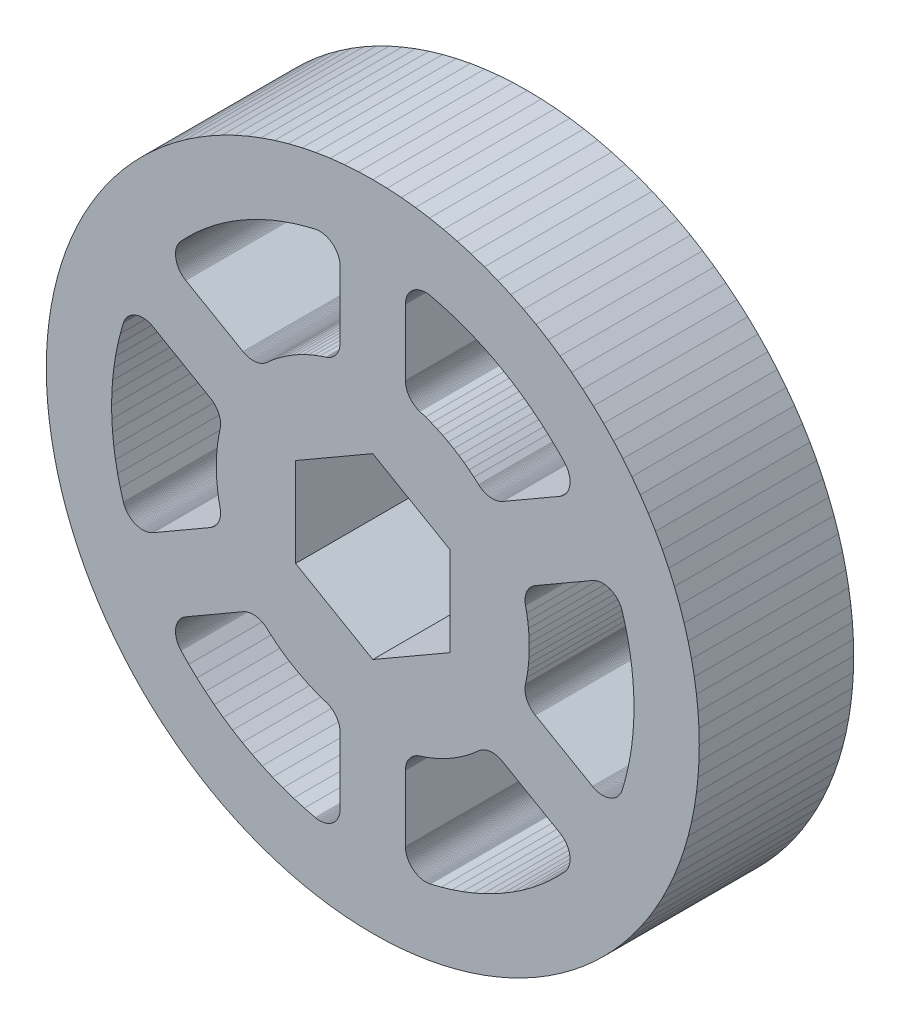
SolidWorks part; units mm, degrees
ref_plane "Front" through (0, 0, 0) normal (0, 0, 1) x (1, 0, 0)
ref_plane "Top" through (0, 0, 0) normal (0, 1, 0) x (1, 0, 0)
ref_plane "Right" through (0, 0, 0) normal (1, 0, 0) x (0, 0, -1)
ref_plane "Plane1" through (0, 0, 12.7) normal (0, 0, 1) x (1, 0, 0)
sketch "Sketch1" plane through (0, 0, 12.7) normal (0, 0, 1) x (1, 0, 0)
  line L0 (19.796, 18.1397) -> (18.9859, 18.9859)
  line L1 (18.9859, 18.9859) -> (18.1397, 19.796)
  line L2 (18.1397, 19.796) -> (17.2589, 20.5684)
  line L3 (17.2589, 20.5684) -> (16.3453, 21.3016)
  line L4 (16.3453, 21.3016) -> (15.4006, 21.9943)
  line L5 (15.4006, 21.9943) -> (14.4265, 22.6451)
  line L6 (14.4265, 22.6451) -> (13.425, 23.2529)
  line L7 (13.425, 23.2529) -> (12.398, 23.8163)
  line L8 (12.398, 23.8163) -> (11.3473, 24.3344)
  line L9 (11.3473, 24.3344) -> (10.2751, 24.8062)
  line L10 (10.2751, 24.8062) -> (9.1833, 25.2308)
  line L11 (9.1833, 25.2308) -> (8.074, 25.6074)
  line L12 (8.074, 25.6074) -> (6.9493, 25.9352)
  line L13 (6.9493, 25.9352) -> (5.8114, 26.2136)
  line L14 (5.8114, 26.2136) -> (4.6625, 26.4422)
  line L15 (4.6625, 26.4422) -> (3.5046, 26.6204)
  line L16 (3.5046, 26.6204) -> (2.3401, 26.7479)
  line L17 (2.3401, 26.7479) -> (1.1712, 26.8245)
  line L18 (1.1712, 26.8245) -> (0, 26.8501)
  line L19 (0, 26.8501) -> (-1.1712, 26.8245)
  line L20 (-1.1712, 26.8245) -> (-2.3401, 26.7479)
  line L21 (-2.3401, 26.7479) -> (-3.5046, 26.6204)
  line L22 (-3.5046, 26.6204) -> (-4.6625, 26.4422)
  line L23 (-4.6625, 26.4422) -> (-5.8114, 26.2136)
  line L24 (-5.8114, 26.2136) -> (-6.9493, 25.9352)
  line L25 (-6.9493, 25.9352) -> (-8.074, 25.6074)
  line L26 (-8.074, 25.6074) -> (-9.1833, 25.2308)
  line L27 (-9.1833, 25.2308) -> (-10.2751, 24.8062)
  line L28 (-10.2751, 24.8062) -> (-11.3473, 24.3344)
  line L29 (-11.3473, 24.3344) -> (-12.398, 23.8163)
  line L30 (-12.398, 23.8163) -> (-13.425, 23.2529)
  line L31 (-13.425, 23.2529) -> (-14.4265, 22.6451)
  line L32 (-14.4265, 22.6451) -> (-15.4006, 21.9943)
  line L33 (-15.4006, 21.9943) -> (-16.3453, 21.3016)
  line L34 (-16.3453, 21.3016) -> (-17.2589, 20.5684)
  line L35 (-17.2589, 20.5684) -> (-18.1397, 19.796)
  line L36 (-18.1397, 19.796) -> (-18.9859, 18.9859)
  line L37 (-18.9859, 18.9859) -> (-19.796, 18.1397)
  line L38 (-19.796, 18.1397) -> (-20.5684, 17.2589)
  line L39 (-20.5684, 17.2589) -> (-21.3016, 16.3453)
  line L40 (-21.3016, 16.3453) -> (-21.9943, 15.4006)
  line L41 (-21.9943, 15.4006) -> (-22.6451, 14.4265)
  line L42 (-22.6451, 14.4265) -> (-23.2529, 13.425)
  line L43 (-23.2529, 13.425) -> (-23.8163, 12.398)
  line L44 (-23.8163, 12.398) -> (-24.3344, 11.3473)
  line L45 (-24.3344, 11.3473) -> (-24.8062, 10.2751)
  line L46 (-24.8062, 10.2751) -> (-25.2308, 9.1833)
  line L47 (-25.2308, 9.1833) -> (-25.6074, 8.074)
  line L48 (-25.6074, 8.074) -> (-25.9352, 6.9493)
  line L49 (-25.9352, 6.9493) -> (-26.2136, 5.8114)
  line L50 (-26.2136, 5.8114) -> (-26.4422, 4.6625)
  line L51 (-26.4422, 4.6625) -> (-26.6204, 3.5046)
  line L52 (-26.6204, 3.5046) -> (-26.7479, 2.3401)
  line L53 (-26.7479, 2.3401) -> (-26.8245, 1.1712)
  line L54 (-26.8245, 1.1712) -> (-26.8501, 0)
  line L55 (-26.8501, 0) -> (-26.8245, -1.1712)
  line L56 (-26.8245, -1.1712) -> (-26.7479, -2.3401)
  line L57 (-26.7479, -2.3401) -> (-26.6204, -3.5046)
  line L58 (-26.6204, -3.5046) -> (-26.4422, -4.6625)
  line L59 (-26.4422, -4.6625) -> (-26.2136, -5.8114)
  line L60 (-26.2136, -5.8114) -> (-25.9352, -6.9493)
  line L61 (-25.9352, -6.9493) -> (-25.6074, -8.074)
  line L62 (-25.6074, -8.074) -> (-25.2308, -9.1833)
  line L63 (-25.2308, -9.1833) -> (-24.8062, -10.2751)
  line L64 (-24.8062, -10.2751) -> (-24.3344, -11.3473)
  line L65 (-24.3344, -11.3473) -> (-23.8163, -12.398)
  line L66 (-23.8163, -12.398) -> (-23.2529, -13.425)
  line L67 (-23.2529, -13.425) -> (-22.6451, -14.4265)
  line L68 (-22.6451, -14.4265) -> (-21.9943, -15.4006)
  line L69 (-21.9943, -15.4006) -> (-21.3016, -16.3453)
  line L70 (-21.3016, -16.3453) -> (-20.5684, -17.2589)
  line L71 (-20.5684, -17.2589) -> (-19.796, -18.1397)
  line L72 (-19.796, -18.1397) -> (-18.9859, -18.9859)
  line L73 (-18.9859, -18.9859) -> (-18.1397, -19.796)
  line L74 (-18.1397, -19.796) -> (-17.2589, -20.5684)
  line L75 (-17.2589, -20.5684) -> (-16.3453, -21.3016)
  line L76 (-16.3453, -21.3016) -> (-15.4006, -21.9943)
  line L77 (-15.4006, -21.9943) -> (-14.4265, -22.6451)
  line L78 (-14.4265, -22.6451) -> (-13.425, -23.2529)
  line L79 (-13.425, -23.2529) -> (-12.398, -23.8163)
  line L80 (-12.398, -23.8163) -> (-11.3473, -24.3344)
  line L81 (-11.3473, -24.3344) -> (-10.2751, -24.8062)
  line L82 (-10.2751, -24.8062) -> (-9.1833, -25.2308)
  line L83 (-9.1833, -25.2308) -> (-8.074, -25.6074)
  line L84 (-8.074, -25.6074) -> (-6.9493, -25.9352)
  line L85 (-6.9493, -25.9352) -> (-5.8114, -26.2136)
  line L86 (-5.8114, -26.2136) -> (-4.6625, -26.4422)
  line L87 (-4.6625, -26.4422) -> (-3.5046, -26.6204)
  line L88 (-3.5046, -26.6204) -> (-2.3401, -26.7479)
  line L89 (-2.3401, -26.7479) -> (-1.1712, -26.8245)
  line L90 (-1.1712, -26.8245) -> (0, -26.8501)
  line L91 (0, -26.8501) -> (1.1712, -26.8245)
  line L92 (1.1712, -26.8245) -> (2.3401, -26.7479)
  line L93 (2.3401, -26.7479) -> (3.5046, -26.6204)
  line L94 (3.5046, -26.6204) -> (4.6625, -26.4422)
  line L95 (4.6625, -26.4422) -> (5.8114, -26.2136)
  line L96 (5.8114, -26.2136) -> (6.9493, -25.9352)
  line L97 (6.9493, -25.9352) -> (8.074, -25.6074)
  line L98 (8.074, -25.6074) -> (9.1833, -25.2308)
  line L99 (9.1833, -25.2308) -> (10.2751, -24.8062)
  line L100 (10.2751, -24.8062) -> (11.3473, -24.3344)
  line L101 (11.3473, -24.3344) -> (12.398, -23.8163)
  line L102 (12.398, -23.8163) -> (13.425, -23.2529)
  line L103 (13.425, -23.2529) -> (14.4265, -22.6451)
  line L104 (14.4265, -22.6451) -> (15.4006, -21.9943)
  line L105 (15.4006, -21.9943) -> (16.3453, -21.3016)
  line L106 (16.3453, -21.3016) -> (17.2589, -20.5684)
  line L107 (17.2589, -20.5684) -> (18.1397, -19.796)
  line L108 (18.1397, -19.796) -> (18.9859, -18.9859)
  line L109 (18.9859, -18.9859) -> (19.796, -18.1397)
  line L110 (19.796, -18.1397) -> (20.5684, -17.2589)
  line L111 (20.5684, -17.2589) -> (21.3016, -16.3453)
  line L112 (21.3016, -16.3453) -> (21.9943, -15.4006)
  line L113 (21.9943, -15.4006) -> (22.6451, -14.4265)
  line L114 (22.6451, -14.4265) -> (23.2529, -13.425)
  line L115 (23.2529, -13.425) -> (23.8163, -12.398)
  line L116 (23.8163, -12.398) -> (24.3344, -11.3473)
  line L117 (24.3344, -11.3473) -> (24.8062, -10.2751)
  line L118 (24.8062, -10.2751) -> (25.2308, -9.1833)
  line L119 (25.2308, -9.1833) -> (25.6074, -8.074)
  line L120 (25.6074, -8.074) -> (25.9352, -6.9493)
  line L121 (25.9352, -6.9493) -> (26.2136, -5.8114)
  line L122 (26.2136, -5.8114) -> (26.4422, -4.6625)
  line L123 (26.4422, -4.6625) -> (26.6204, -3.5046)
  line L124 (26.6204, -3.5046) -> (26.7479, -2.3401)
  line L125 (26.7479, -2.3401) -> (26.8245, -1.1712)
  line L126 (26.8245, -1.1712) -> (26.8501, 0)
  line L127 (26.8501, 0) -> (26.8245, 1.1712)
  line L128 (26.8245, 1.1712) -> (26.7479, 2.3401)
  line L129 (26.7479, 2.3401) -> (26.6204, 3.5046)
  line L130 (26.6204, 3.5046) -> (26.4422, 4.6625)
  line L131 (26.4422, 4.6625) -> (26.2136, 5.8114)
  line L132 (26.2136, 5.8114) -> (25.9352, 6.9493)
  line L133 (25.9352, 6.9493) -> (25.6074, 8.074)
  line L134 (25.6074, 8.074) -> (25.2308, 9.1833)
  line L135 (25.2308, 9.1833) -> (24.8062, 10.2751)
  line L136 (24.8062, 10.2751) -> (24.3344, 11.3473)
  line L137 (24.3344, 11.3473) -> (23.8163, 12.398)
  line L138 (23.8163, 12.398) -> (23.2529, 13.425)
  line L139 (23.2529, 13.425) -> (22.6451, 14.4265)
  line L140 (22.6451, 14.4265) -> (21.9943, 15.4006)
  line L141 (21.9943, 15.4006) -> (21.3016, 16.3453)
  line L142 (21.3016, 16.3453) -> (20.5684, 17.2589)
  line L143 (20.5684, 17.2589) -> (19.796, 18.1397)
  line L144 (13.7695, 16.4862) -> (14.4665, 15.8781)
  line L145 (14.4665, 15.8781) -> (15.1366, 15.2406)
  line L146 (15.1366, 15.2406) -> (15.7787, 14.5749)
  line L147 (15.7787, 14.5749) -> (15.8261, 14.5212)
  line L148 (15.8261, 14.5212) -> (15.8713, 14.4656)
  line L149 (15.8713, 14.4656) -> (15.914, 14.4081)
  line L150 (15.914, 14.4081) -> (15.9542, 14.3489)
  line L151 (15.9542, 14.3489) -> (15.9919, 14.2879)
  line L152 (15.9919, 14.2879) -> (16.0269, 14.2254)
  line L153 (16.0269, 14.2254) -> (16.0592, 14.1615)
  line L154 (16.0592, 14.1615) -> (16.0888, 14.0963)
  line L155 (16.0888, 14.0963) -> (16.1156, 14.0298)
  line L156 (16.1156, 14.0298) -> (16.1395, 13.9623)
  line L157 (16.1395, 13.9623) -> (16.1605, 13.8938)
  line L158 (16.1605, 13.8938) -> (16.1785, 13.8245)
  line L159 (16.1785, 13.8245) -> (16.1936, 13.7545)
  line L160 (16.1936, 13.7545) -> (16.2057, 13.6839)
  line L161 (16.2057, 13.6839) -> (16.2148, 13.6128)
  line L162 (16.2148, 13.6128) -> (16.2208, 13.5414)
  line L163 (16.2208, 13.5414) -> (16.2237, 13.4699)
  line L164 (16.2237, 13.4699) -> (16.2236, 13.3982)
  line L165 (16.2236, 13.3982) -> (16.2205, 13.3267)
  line L166 (16.2205, 13.3267) -> (16.2143, 13.2553)
  line L167 (16.2143, 13.2553) -> (16.2051, 13.1843)
  line L168 (16.2051, 13.1843) -> (16.1928, 13.1137)
  line L169 (16.1928, 13.1137) -> (16.1775, 13.0437)
  line L170 (16.1775, 13.0437) -> (16.1593, 12.9744)
  line L171 (16.1593, 12.9744) -> (16.1381, 12.906)
  line L172 (16.1381, 12.906) -> (16.114, 12.8385)
  line L173 (16.114, 12.8385) -> (16.0871, 12.7722)
  line L174 (16.0871, 12.7722) -> (16.0573, 12.707)
  line L175 (16.0573, 12.707) -> (16.0248, 12.6431)
  line L176 (16.0248, 12.6431) -> (15.9897, 12.5808)
  line L177 (15.9897, 12.5808) -> (15.9518, 12.5199)
  line L178 (15.9518, 12.5199) -> (15.9114, 12.4608)
  line L179 (15.9114, 12.4608) -> (15.8686, 12.4034)
  line L180 (15.8686, 12.4034) -> (15.8233, 12.3479)
  line L181 (15.8233, 12.3479) -> (15.7757, 12.2943)
  line L182 (15.7757, 12.2943) -> (15.7258, 12.2429)
  line L183 (15.7258, 12.2429) -> (15.6738, 12.1936)
  line L184 (15.6738, 12.1936) -> (15.6198, 12.1466)
  line L185 (15.6198, 12.1466) -> (15.5638, 12.102)
  line L186 (15.5638, 12.102) -> (15.5059, 12.0598)
  line L187 (15.5059, 12.0598) -> (15.4463, 12.0201)
  line L188 (15.4463, 12.0201) -> (15.385, 11.9829)
  line L189 (15.385, 11.9829) -> (10.6753, 9.2637)
  line L190 (10.6753, 9.2637) -> (10.6132, 9.2296)
  line L191 (10.6132, 9.2296) -> (10.5497, 9.1982)
  line L192 (10.5497, 9.1982) -> (10.485, 9.1694)
  line L193 (10.485, 9.1694) -> (10.4191, 9.1434)
  line L194 (10.4191, 9.1434) -> (10.3522, 9.1202)
  line L195 (10.3522, 9.1202) -> (10.2844, 9.0999)
  line L196 (10.2844, 9.0999) -> (10.2158, 9.0824)
  line L197 (10.2158, 9.0824) -> (10.1465, 9.0678)
  line L198 (10.1465, 9.0678) -> (10.0766, 9.0562)
  line L199 (10.0766, 9.0562) -> (10.0063, 9.0476)
  line L200 (10.0063, 9.0476) -> (9.9357, 9.0419)
  line L201 (9.9357, 9.0419) -> (9.8649, 9.0392)
  line L202 (9.8649, 9.0392) -> (9.7941, 9.0394)
  line L203 (9.7941, 9.0394) -> (9.7234, 9.0427)
  line L204 (9.7234, 9.0427) -> (9.6528, 9.049)
  line L205 (9.6528, 9.049) -> (9.5826, 9.0582)
  line L206 (9.5826, 9.0582) -> (9.5128, 9.0704)
  line L207 (9.5128, 9.0704) -> (9.4437, 9.0855)
  line L208 (9.4437, 9.0855) -> (9.3752, 9.1035)
  line L209 (9.3752, 9.1035) -> (9.3075, 9.1244)
  line L210 (9.3075, 9.1244) -> (9.2408, 9.1481)
  line L211 (9.2408, 9.1481) -> (9.1751, 9.1746)
  line L212 (9.1751, 9.1746) -> (9.1106, 9.2039)
  line L213 (9.1106, 9.2039) -> (9.0474, 9.2359)
  line L214 (9.0474, 9.2359) -> (8.9856, 9.2705)
  line L215 (8.9856, 9.2705) -> (8.9253, 9.3076)
  line L216 (8.9253, 9.3076) -> (8.8667, 9.3473)
  line L217 (8.8667, 9.3473) -> (8.8097, 9.3894)
  line L218 (8.8097, 9.3894) -> (8.7546, 9.4339)
  line L219 (8.7546, 9.4339) -> (8.7015, 9.4807)
  line L220 (8.7015, 9.4807) -> (8.3172, 9.8195)
  line L221 (8.3172, 9.8195) -> (7.9198, 10.1428)
  line L222 (7.9198, 10.1428) -> (7.5098, 10.45)
  line L223 (7.5098, 10.45) -> (7.0879, 10.7406)
  line L224 (7.0879, 10.7406) -> (6.6548, 11.0142)
  line L225 (6.6548, 11.0142) -> (6.2112, 11.2704)
  line L226 (6.2112, 11.2704) -> (5.7577, 11.5086)
  line L227 (5.7577, 11.5086) -> (5.295, 11.7287)
  line L228 (5.295, 11.7287) -> (4.824, 11.9301)
  line L229 (4.824, 11.9301) -> (4.3454, 12.1127)
  line L230 (4.3454, 12.1127) -> (3.8598, 12.2761)
  line L231 (3.8598, 12.2761) -> (3.7927, 12.2987)
  line L232 (3.7927, 12.2987) -> (3.7266, 12.3242)
  line L233 (3.7266, 12.3242) -> (3.6617, 12.3524)
  line L234 (3.6617, 12.3524) -> (3.598, 12.3834)
  line L235 (3.598, 12.3834) -> (3.5356, 12.417)
  line L236 (3.5356, 12.417) -> (3.4748, 12.4532)
  line L237 (3.4748, 12.4532) -> (3.4155, 12.492)
  line L238 (3.4155, 12.492) -> (3.3579, 12.5332)
  line L239 (3.3579, 12.5332) -> (3.3021, 12.5768)
  line L240 (3.3021, 12.5768) -> (3.2482, 12.6227)
  line L241 (3.2482, 12.6227) -> (3.1963, 12.6709)
  line L242 (3.1963, 12.6709) -> (3.1464, 12.7212)
  line L243 (3.1464, 12.7212) -> (3.0987, 12.7735)
  line L244 (3.0987, 12.7735) -> (3.0533, 12.8279)
  line L245 (3.0533, 12.8279) -> (3.0102, 12.8841)
  line L246 (3.0102, 12.8841) -> (2.9695, 12.942)
  line L247 (2.9695, 12.942) -> (2.9313, 13.0017)
  line L248 (2.9313, 13.0017) -> (2.8957, 13.0629)
  line L249 (2.8957, 13.0629) -> (2.8626, 13.1255)
  line L250 (2.8626, 13.1255) -> (2.8323, 13.1895)
  line L251 (2.8323, 13.1895) -> (2.8046, 13.2547)
  line L252 (2.8046, 13.2547) -> (2.7798, 13.321)
  line L253 (2.7798, 13.321) -> (2.7577, 13.3883)
  line L254 (2.7577, 13.3883) -> (2.7385, 13.4565)
  line L255 (2.7385, 13.4565) -> (2.7222, 13.5254)
  line L256 (2.7222, 13.5254) -> (2.7089, 13.595)
  line L257 (2.7089, 13.595) -> (2.6984, 13.665)
  line L258 (2.6984, 13.665) -> (2.691, 13.7354)
  line L259 (2.691, 13.7354) -> (2.6865, 13.8061)
  line L260 (2.6865, 13.8061) -> (2.685, 13.8769)
  line L261 (2.685, 13.8769) -> (2.685, 19.3153)
  line L262 (2.685, 19.3153) -> (2.6865, 19.3869)
  line L263 (2.6865, 19.3869) -> (2.6911, 19.4584)
  line L264 (2.6911, 19.4584) -> (2.6988, 19.5296)
  line L265 (2.6988, 19.5296) -> (2.7094, 19.6004)
  line L266 (2.7094, 19.6004) -> (2.7231, 19.6708)
  line L267 (2.7231, 19.6708) -> (2.7398, 19.7404)
  line L268 (2.7398, 19.7404) -> (2.7594, 19.8093)
  line L269 (2.7594, 19.8093) -> (2.7819, 19.8773)
  line L270 (2.7819, 19.8773) -> (2.8073, 19.9443)
  line L271 (2.8073, 19.9443) -> (2.8356, 20.0101)
  line L272 (2.8356, 20.0101) -> (2.8667, 20.0747)
  line L273 (2.8667, 20.0747) -> (2.9004, 20.1378)
  line L274 (2.9004, 20.1378) -> (2.9369, 20.1995)
  line L275 (2.9369, 20.1995) -> (2.9759, 20.2596)
  line L276 (2.9759, 20.2596) -> (3.0175, 20.3179)
  line L277 (3.0175, 20.3179) -> (3.0615, 20.3744)
  line L278 (3.0615, 20.3744) -> (3.1079, 20.429)
  line L279 (3.1079, 20.429) -> (3.1565, 20.4816)
  line L280 (3.1565, 20.4816) -> (3.2074, 20.532)
  line L281 (3.2074, 20.532) -> (3.2604, 20.5802)
  line L282 (3.2604, 20.5802) -> (3.3154, 20.6261)
  line L283 (3.3154, 20.6261) -> (3.3723, 20.6696)
  line L284 (3.3723, 20.6696) -> (3.431, 20.7107)
  line L285 (3.431, 20.7107) -> (3.4914, 20.7492)
  line L286 (3.4914, 20.7492) -> (3.5534, 20.7851)
  line L287 (3.5534, 20.7851) -> (3.6168, 20.8183)
  line L288 (3.6168, 20.8183) -> (3.6817, 20.8488)
  line L289 (3.6817, 20.8488) -> (3.7477, 20.8765)
  line L290 (3.7477, 20.8765) -> (3.8149, 20.9013)
  line L291 (3.8149, 20.9013) -> (3.8831, 20.9233)
  line L292 (3.8831, 20.9233) -> (3.9522, 20.9423)
  line L293 (3.9522, 20.9423) -> (4.022, 20.9584)
  line L294 (4.022, 20.9584) -> (4.0924, 20.9714)
  line L295 (4.0924, 20.9714) -> (4.1633, 20.9815)
  line L296 (4.1633, 20.9815) -> (4.2346, 20.9885)
  line L297 (4.2346, 20.9885) -> (4.3061, 20.9924)
  line L298 (4.3061, 20.9924) -> (4.3778, 20.9933)
  line L299 (4.3778, 20.9933) -> (4.4494, 20.9912)
  line L300 (4.4494, 20.9912) -> (4.5208, 20.986)
  line L301 (4.5208, 20.986) -> (4.592, 20.9777)
  line L302 (4.592, 20.9777) -> (4.6627, 20.9664)
  line L303 (4.6627, 20.9664) -> (4.7329, 20.9522)
  line L304 (4.7329, 20.9522) -> (5.6305, 20.729)
  line L305 (5.6305, 20.729) -> (6.5176, 20.4674)
  line L306 (6.5176, 20.4674) -> (7.3927, 20.1678)
  line L307 (7.3927, 20.1678) -> (8.254, 19.8309)
  line L308 (8.254, 19.8309) -> (9.1001, 19.4572)
  line L309 (9.1001, 19.4572) -> (9.9293, 19.0474)
  line L310 (9.9293, 19.0474) -> (10.74, 18.6023)
  line L311 (10.74, 18.6023) -> (11.5309, 18.1227)
  line L312 (11.5309, 18.1227) -> (12.3004, 17.6095)
  line L313 (12.3004, 17.6095) -> (13.047, 17.0637)
  line L314 (13.047, 17.0637) -> (13.7695, 16.4862)
  line L315 (16.1936, -13.7545) -> (16.1785, -13.8245)
  line L316 (16.1785, -13.8245) -> (16.1605, -13.8938)
  line L317 (16.1605, -13.8938) -> (16.1395, -13.9623)
  line L318 (16.1395, -13.9623) -> (16.1156, -14.0298)
  line L319 (16.1156, -14.0298) -> (16.0888, -14.0963)
  line L320 (16.0888, -14.0963) -> (16.0592, -14.1615)
  line L321 (16.0592, -14.1615) -> (16.0269, -14.2254)
  line L322 (16.0269, -14.2254) -> (15.9919, -14.2879)
  line L323 (15.9919, -14.2879) -> (15.9542, -14.3489)
  line L324 (15.9542, -14.3489) -> (15.914, -14.4081)
  line L325 (15.914, -14.4081) -> (15.8713, -14.4656)
  line L326 (15.8713, -14.4656) -> (15.8261, -14.5212)
  line L327 (15.8261, -14.5212) -> (15.7787, -14.5749)
  line L328 (15.7787, -14.5749) -> (15.1366, -15.2406)
  line L329 (15.1366, -15.2406) -> (14.4665, -15.8781)
  line L330 (14.4665, -15.8781) -> (13.7695, -16.4862)
  line L331 (13.7695, -16.4862) -> (13.047, -17.0637)
  line L332 (13.047, -17.0637) -> (12.3004, -17.6095)
  line L333 (12.3004, -17.6095) -> (11.5309, -18.1227)
  line L334 (11.5309, -18.1227) -> (10.74, -18.6023)
  line L335 (10.74, -18.6023) -> (9.9293, -19.0474)
  line L336 (9.9293, -19.0474) -> (9.1001, -19.4572)
  line L337 (9.1001, -19.4572) -> (8.254, -19.8309)
  line L338 (8.254, -19.8309) -> (7.3927, -20.1678)
  line L339 (7.3927, -20.1678) -> (6.5176, -20.4674)
  line L340 (6.5176, -20.4674) -> (5.6305, -20.729)
  line L341 (5.6305, -20.729) -> (4.7329, -20.9522)
  line L342 (4.7329, -20.9522) -> (4.6627, -20.9664)
  line L343 (4.6627, -20.9664) -> (4.592, -20.9777)
  line L344 (4.592, -20.9777) -> (4.5208, -20.986)
  line L345 (4.5208, -20.986) -> (4.4494, -20.9912)
  line L346 (4.4494, -20.9912) -> (4.3778, -20.9933)
  line L347 (4.3778, -20.9933) -> (4.3061, -20.9924)
  line L348 (4.3061, -20.9924) -> (4.2346, -20.9885)
  line L349 (4.2346, -20.9885) -> (4.1633, -20.9815)
  line L350 (4.1633, -20.9815) -> (4.0924, -20.9714)
  line L351 (4.0924, -20.9714) -> (4.022, -20.9584)
  line L352 (4.022, -20.9584) -> (3.9522, -20.9423)
  line L353 (3.9522, -20.9423) -> (3.8831, -20.9233)
  line L354 (3.8831, -20.9233) -> (3.8149, -20.9013)
  line L355 (3.8149, -20.9013) -> (3.7477, -20.8765)
  line L356 (3.7477, -20.8765) -> (3.6817, -20.8488)
  line L357 (3.6817, -20.8488) -> (3.6168, -20.8183)
  line L358 (3.6168, -20.8183) -> (3.5534, -20.7851)
  line L359 (3.5534, -20.7851) -> (3.4914, -20.7492)
  line L360 (3.4914, -20.7492) -> (3.431, -20.7107)
  line L361 (3.431, -20.7107) -> (3.3723, -20.6696)
  line L362 (3.3723, -20.6696) -> (3.3154, -20.6261)
  line L363 (3.3154, -20.6261) -> (3.2604, -20.5802)
  line L364 (3.2604, -20.5802) -> (3.2074, -20.532)
  line L365 (3.2074, -20.532) -> (3.1565, -20.4816)
  line L366 (3.1565, -20.4816) -> (3.1079, -20.429)
  line L367 (3.1079, -20.429) -> (3.0615, -20.3744)
  line L368 (3.0615, -20.3744) -> (3.0175, -20.3179)
  line L369 (3.0175, -20.3179) -> (2.9759, -20.2596)
  line L370 (2.9759, -20.2596) -> (2.9369, -20.1995)
  line L371 (2.9369, -20.1995) -> (2.9004, -20.1378)
  line L372 (2.9004, -20.1378) -> (2.8667, -20.0747)
  line L373 (2.8667, -20.0747) -> (2.8356, -20.0101)
  line L374 (2.8356, -20.0101) -> (2.8073, -19.9443)
  line L375 (2.8073, -19.9443) -> (2.7819, -19.8773)
  line L376 (2.7819, -19.8773) -> (2.7594, -19.8093)
  line L377 (2.7594, -19.8093) -> (2.7398, -19.7404)
  line L378 (2.7398, -19.7404) -> (2.7231, -19.6708)
  line L379 (2.7231, -19.6708) -> (2.7094, -19.6004)
  line L380 (2.7094, -19.6004) -> (2.6988, -19.5296)
  line L381 (2.6988, -19.5296) -> (2.6911, -19.4584)
  line L382 (2.6911, -19.4584) -> (2.6865, -19.3869)
  line L383 (2.6865, -19.3869) -> (2.685, -19.3153)
  line L384 (2.685, -19.3153) -> (2.685, -13.8769)
  line L385 (2.685, -13.8769) -> (2.6865, -13.8061)
  line L386 (2.6865, -13.8061) -> (2.691, -13.7354)
  line L387 (2.691, -13.7354) -> (2.6984, -13.665)
  line L388 (2.6984, -13.665) -> (2.7089, -13.595)
  line L389 (2.7089, -13.595) -> (2.7222, -13.5254)
  line L390 (2.7222, -13.5254) -> (2.7385, -13.4565)
  line L391 (2.7385, -13.4565) -> (2.7577, -13.3883)
  line L392 (2.7577, -13.3883) -> (2.7798, -13.321)
  line L393 (2.7798, -13.321) -> (2.8046, -13.2547)
  line L394 (2.8046, -13.2547) -> (2.8323, -13.1895)
  line L395 (2.8323, -13.1895) -> (2.8626, -13.1255)
  line L396 (2.8626, -13.1255) -> (2.8957, -13.0629)
  line L397 (2.8957, -13.0629) -> (2.9313, -13.0017)
  line L398 (2.9313, -13.0017) -> (2.9695, -12.942)
  line L399 (2.9695, -12.942) -> (3.0102, -12.8841)
  line L400 (3.0102, -12.8841) -> (3.0533, -12.8279)
  line L401 (3.0533, -12.8279) -> (3.0987, -12.7735)
  line L402 (3.0987, -12.7735) -> (3.1464, -12.7212)
  line L403 (3.1464, -12.7212) -> (3.1963, -12.6709)
  line L404 (3.1963, -12.6709) -> (3.2482, -12.6227)
  line L405 (3.2482, -12.6227) -> (3.3021, -12.5768)
  line L406 (3.3021, -12.5768) -> (3.3579, -12.5332)
  line L407 (3.3579, -12.5332) -> (3.4155, -12.492)
  line L408 (3.4155, -12.492) -> (3.4748, -12.4532)
  line L409 (3.4748, -12.4532) -> (3.5356, -12.417)
  line L410 (3.5356, -12.417) -> (3.598, -12.3834)
  line L411 (3.598, -12.3834) -> (3.6617, -12.3524)
  line L412 (3.6617, -12.3524) -> (3.7266, -12.3242)
  line L413 (3.7266, -12.3242) -> (3.7927, -12.2987)
  line L414 (3.7927, -12.2987) -> (3.8598, -12.2761)
  line L415 (3.8598, -12.2761) -> (4.3454, -12.1127)
  line L416 (4.3454, -12.1127) -> (4.824, -11.9301)
  line L417 (4.824, -11.9301) -> (5.295, -11.7287)
  line L418 (5.295, -11.7287) -> (5.7577, -11.5086)
  line L419 (5.7577, -11.5086) -> (6.2112, -11.2704)
  line L420 (6.2112, -11.2704) -> (6.6548, -11.0142)
  line L421 (6.6548, -11.0142) -> (7.0879, -10.7406)
  line L422 (7.0879, -10.7406) -> (7.5098, -10.45)
  line L423 (7.5098, -10.45) -> (7.9198, -10.1428)
  line L424 (7.9198, -10.1428) -> (8.3172, -9.8195)
  line L425 (8.3172, -9.8195) -> (8.7015, -9.4807)
  line L426 (8.7015, -9.4807) -> (8.7546, -9.4339)
  line L427 (8.7546, -9.4339) -> (8.8097, -9.3894)
  line L428 (8.8097, -9.3894) -> (8.8667, -9.3473)
  line L429 (8.8667, -9.3473) -> (8.9253, -9.3076)
  line L430 (8.9253, -9.3076) -> (8.9856, -9.2705)
  line L431 (8.9856, -9.2705) -> (9.0474, -9.2359)
  line L432 (9.0474, -9.2359) -> (9.1106, -9.2039)
  line L433 (9.1106, -9.2039) -> (9.1751, -9.1746)
  line L434 (9.1751, -9.1746) -> (9.2408, -9.1481)
  line L435 (9.2408, -9.1481) -> (9.3075, -9.1244)
  line L436 (9.3075, -9.1244) -> (9.3752, -9.1035)
  line L437 (9.3752, -9.1035) -> (9.4437, -9.0855)
  line L438 (9.4437, -9.0855) -> (9.5128, -9.0704)
  line L439 (9.5128, -9.0704) -> (9.5826, -9.0582)
  line L440 (9.5826, -9.0582) -> (9.6528, -9.049)
  line L441 (9.6528, -9.049) -> (9.7234, -9.0427)
  line L442 (9.7234, -9.0427) -> (9.7941, -9.0394)
  line L443 (9.7941, -9.0394) -> (9.8649, -9.0392)
  line L444 (9.8649, -9.0392) -> (9.9357, -9.0419)
  line L445 (9.9357, -9.0419) -> (10.0063, -9.0476)
  line L446 (10.0063, -9.0476) -> (10.0766, -9.0562)
  line L447 (10.0766, -9.0562) -> (10.1465, -9.0678)
  line L448 (10.1465, -9.0678) -> (10.2158, -9.0824)
  line L449 (10.2158, -9.0824) -> (10.2844, -9.0999)
  line L450 (10.2844, -9.0999) -> (10.3522, -9.1202)
  line L451 (10.3522, -9.1202) -> (10.4191, -9.1434)
  line L452 (10.4191, -9.1434) -> (10.485, -9.1694)
  line L453 (10.485, -9.1694) -> (10.5497, -9.1982)
  line L454 (10.5497, -9.1982) -> (10.6132, -9.2296)
  line L455 (10.6132, -9.2296) -> (10.6753, -9.2637)
  line L456 (10.6753, -9.2637) -> (15.385, -11.9829)
  line L457 (15.385, -11.9829) -> (15.4463, -12.0201)
  line L458 (15.4463, -12.0201) -> (15.5059, -12.0598)
  line L459 (15.5059, -12.0598) -> (15.5638, -12.102)
  line L460 (15.5638, -12.102) -> (15.6198, -12.1466)
  line L461 (15.6198, -12.1466) -> (15.6738, -12.1936)
  line L462 (15.6738, -12.1936) -> (15.7258, -12.2429)
  line L463 (15.7258, -12.2429) -> (15.7757, -12.2943)
  line L464 (15.7757, -12.2943) -> (15.8233, -12.3479)
  line L465 (15.8233, -12.3479) -> (15.8686, -12.4034)
  line L466 (15.8686, -12.4034) -> (15.9114, -12.4608)
  line L467 (15.9114, -12.4608) -> (15.9518, -12.5199)
  line L468 (15.9518, -12.5199) -> (15.9897, -12.5808)
  line L469 (15.9897, -12.5808) -> (16.0248, -12.6431)
  line L470 (16.0248, -12.6431) -> (16.0573, -12.707)
  line L471 (16.0573, -12.707) -> (16.0871, -12.7722)
  line L472 (16.0871, -12.7722) -> (16.114, -12.8385)
  line L473 (16.114, -12.8385) -> (16.1381, -12.906)
  line L474 (16.1381, -12.906) -> (16.1593, -12.9744)
  line L475 (16.1593, -12.9744) -> (16.1775, -13.0437)
  line L476 (16.1775, -13.0437) -> (16.1928, -13.1137)
  line L477 (16.1928, -13.1137) -> (16.2051, -13.1843)
  line L478 (16.2051, -13.1843) -> (16.2143, -13.2553)
  line L479 (16.2143, -13.2553) -> (16.2205, -13.3267)
  line L480 (16.2205, -13.3267) -> (16.2236, -13.3982)
  line L481 (16.2236, -13.3982) -> (16.2237, -13.4699)
  line L482 (16.2237, -13.4699) -> (16.2208, -13.5414)
  line L483 (16.2208, -13.5414) -> (16.2148, -13.6128)
  line L484 (16.2148, -13.6128) -> (16.2057, -13.6839)
  line L485 (16.2057, -13.6839) -> (16.1936, -13.7545)
  line L486 (21.1622, -3.6817) -> (20.9841, -4.5893)
  line L487 (20.9841, -4.5893) -> (20.7671, -5.4884)
  line L488 (20.7671, -5.4884) -> (20.5116, -6.3773)
  line L489 (20.5116, -6.3773) -> (20.4888, -6.4452)
  line L490 (20.4888, -6.4452) -> (20.4632, -6.5121)
  line L491 (20.4632, -6.5121) -> (20.4348, -6.5779)
  line L492 (20.4348, -6.5779) -> (20.4036, -6.6423)
  line L493 (20.4036, -6.6423) -> (20.3696, -6.7054)
  line L494 (20.3696, -6.7054) -> (20.333, -6.767)
  line L495 (20.333, -6.767) -> (20.2939, -6.827)
  line L496 (20.2939, -6.827) -> (20.2521, -6.8852)
  line L497 (20.2521, -6.8852) -> (20.208, -6.9416)
  line L498 (20.208, -6.9416) -> (20.1615, -6.9961)
  line L499 (20.1615, -6.9961) -> (20.1126, -7.0485)
  line L500 (20.1126, -7.0485) -> (20.0616, -7.0988)
  line L501 (20.0616, -7.0988) -> (20.0085, -7.1469)
  line L502 (20.0085, -7.1469) -> (19.9534, -7.1926)
  line L503 (19.9534, -7.1926) -> (19.8964, -7.236)
  line L504 (19.8964, -7.236) -> (19.8376, -7.2769)
  line L505 (19.8376, -7.2769) -> (19.7771, -7.3152)
  line L506 (19.7771, -7.3152) -> (19.715, -7.351)
  line L507 (19.715, -7.351) -> (19.6515, -7.384)
  line L508 (19.6515, -7.384) -> (19.5866, -7.4143)
  line L509 (19.5866, -7.4143) -> (19.5204, -7.4419)
  line L510 (19.5204, -7.4419) -> (19.4532, -7.4665)
  line L511 (19.4532, -7.4665) -> (19.3849, -7.4883)
  line L512 (19.3849, -7.4883) -> (19.3158, -7.5071)
  line L513 (19.3158, -7.5071) -> (19.246, -7.523)
  line L514 (19.246, -7.523) -> (19.1755, -7.5359)
  line L515 (19.1755, -7.5359) -> (19.1046, -7.5458)
  line L516 (19.1046, -7.5458) -> (19.0332, -7.5526)
  line L517 (19.0332, -7.5526) -> (18.9617, -7.5563)
  line L518 (18.9617, -7.5563) -> (18.8901, -7.5571)
  line L519 (18.8901, -7.5571) -> (18.8185, -7.5547)
  line L520 (18.8185, -7.5547) -> (18.7471, -7.5493)
  line L521 (18.7471, -7.5493) -> (18.6759, -7.5409)
  line L522 (18.6759, -7.5409) -> (18.6052, -7.5294)
  line L523 (18.6052, -7.5294) -> (18.5351, -7.515)
  line L524 (18.5351, -7.515) -> (18.4656, -7.4975)
  line L525 (18.4656, -7.4975) -> (18.3969, -7.4771)
  line L526 (18.3969, -7.4771) -> (18.3292, -7.4538)
  line L527 (18.3292, -7.4538) -> (18.2625, -7.4276)
  line L528 (18.2625, -7.4276) -> (18.197, -7.3986)
  line L529 (18.197, -7.3986) -> (18.1328, -7.3668)
  line L530 (18.1328, -7.3668) -> (18.07, -7.3323)
  line L531 (18.07, -7.3323) -> (13.3603, -4.6132)
  line L532 (13.3603, -4.6132) -> (13.2997, -4.5765)
  line L533 (13.2997, -4.5765) -> (13.2407, -4.5373)
  line L534 (13.2407, -4.5373) -> (13.1835, -4.4956)
  line L535 (13.1835, -4.4956) -> (13.128, -4.4515)
  line L536 (13.128, -4.4515) -> (13.0745, -4.4052)
  line L537 (13.0745, -4.4052) -> (13.0229, -4.3566)
  line L538 (13.0229, -4.3566) -> (12.9735, -4.3059)
  line L539 (12.9735, -4.3059) -> (12.9262, -4.2532)
  line L540 (12.9262, -4.2532) -> (12.8812, -4.1985)
  line L541 (12.8812, -4.1985) -> (12.8386, -4.1419)
  line L542 (12.8386, -4.1419) -> (12.7983, -4.0836)
  line L543 (12.7983, -4.0836) -> (12.7606, -4.0237)
  line L544 (12.7606, -4.0237) -> (12.7254, -3.9622)
  line L545 (12.7254, -3.9622) -> (12.6929, -3.8993)
  line L546 (12.6929, -3.8993) -> (12.663, -3.8351)
  line L547 (12.663, -3.8351) -> (12.6359, -3.7697)
  line L548 (12.6359, -3.7697) -> (12.6116, -3.7032)
  line L549 (12.6116, -3.7032) -> (12.5901, -3.6357)
  line L550 (12.5901, -3.6357) -> (12.5714, -3.5674)
  line L551 (12.5714, -3.5674) -> (12.5557, -3.4983)
  line L552 (12.5557, -3.4983) -> (12.5429, -3.4287)
  line L553 (12.5429, -3.4287) -> (12.533, -3.3586)
  line L554 (12.533, -3.3586) -> (12.5261, -3.2881)
  line L555 (12.5261, -3.2881) -> (12.5222, -3.2174)
  line L556 (12.5222, -3.2174) -> (12.5213, -3.1465)
  line L557 (12.5213, -3.1465) -> (12.5233, -3.0758)
  line L558 (12.5233, -3.0758) -> (12.5284, -3.0051)
  line L559 (12.5284, -3.0051) -> (12.5364, -2.9347)
  line L560 (12.5364, -2.9347) -> (12.5473, -2.8648)
  line L561 (12.5473, -2.8648) -> (12.5613, -2.7953)
  line L562 (12.5613, -2.7953) -> (12.6626, -2.2932)
  line L563 (12.6626, -2.2932) -> (12.7438, -1.7874)
  line L564 (12.7438, -1.7874) -> (12.8049, -1.2787)
  line L565 (12.8049, -1.2787) -> (12.8456, -0.768)
  line L566 (12.8456, -0.768) -> (12.866, -0.2561)
  line L567 (12.866, -0.2561) -> (12.866, 0.2561)
  line L568 (12.866, 0.2561) -> (12.8456, 0.768)
  line L569 (12.8456, 0.768) -> (12.8049, 1.2787)
  line L570 (12.8049, 1.2787) -> (12.7438, 1.7873)
  line L571 (12.7438, 1.7873) -> (12.6626, 2.2932)
  line L572 (12.6626, 2.2932) -> (12.5613, 2.7953)
  line L573 (12.5613, 2.7953) -> (12.5473, 2.8648)
  line L574 (12.5473, 2.8648) -> (12.5364, 2.9347)
  line L575 (12.5364, 2.9347) -> (12.5284, 3.0051)
  line L576 (12.5284, 3.0051) -> (12.5233, 3.0758)
  line L577 (12.5233, 3.0758) -> (12.5213, 3.1465)
  line L578 (12.5213, 3.1465) -> (12.5222, 3.2174)
  line L579 (12.5222, 3.2174) -> (12.5261, 3.2881)
  line L580 (12.5261, 3.2881) -> (12.533, 3.3586)
  line L581 (12.533, 3.3586) -> (12.5429, 3.4287)
  line L582 (12.5429, 3.4287) -> (12.5557, 3.4983)
  line L583 (12.5557, 3.4983) -> (12.5714, 3.5674)
  line L584 (12.5714, 3.5674) -> (12.5901, 3.6357)
  line L585 (12.5901, 3.6357) -> (12.6116, 3.7032)
  line L586 (12.6116, 3.7032) -> (12.6359, 3.7697)
  line L587 (12.6359, 3.7697) -> (12.663, 3.8351)
  line L588 (12.663, 3.8351) -> (12.6929, 3.8993)
  line L589 (12.6929, 3.8993) -> (12.7254, 3.9622)
  line L590 (12.7254, 3.9622) -> (12.7606, 4.0237)
  line L591 (12.7606, 4.0237) -> (12.7983, 4.0836)
  line L592 (12.7983, 4.0836) -> (12.8386, 4.1419)
  line L593 (12.8386, 4.1419) -> (12.8812, 4.1985)
  line L594 (12.8812, 4.1985) -> (12.9262, 4.2532)
  line L595 (12.9262, 4.2532) -> (12.9735, 4.3059)
  line L596 (12.9735, 4.3059) -> (13.0229, 4.3566)
  line L597 (13.0229, 4.3566) -> (13.0745, 4.4052)
  line L598 (13.0745, 4.4052) -> (13.128, 4.4515)
  line L599 (13.128, 4.4515) -> (13.1835, 4.4956)
  line L600 (13.1835, 4.4956) -> (13.2407, 4.5373)
  line L601 (13.2407, 4.5373) -> (13.2997, 4.5765)
  line L602 (13.2997, 4.5765) -> (13.3603, 4.6132)
  line L603 (13.3603, 4.6132) -> (18.07, 7.3323)
  line L604 (18.07, 7.3323) -> (18.1328, 7.3668)
  line L605 (18.1328, 7.3668) -> (18.197, 7.3986)
  line L606 (18.197, 7.3986) -> (18.2625, 7.4276)
  line L607 (18.2625, 7.4276) -> (18.3292, 7.4538)
  line L608 (18.3292, 7.4538) -> (18.3969, 7.4771)
  line L609 (18.3969, 7.4771) -> (18.4656, 7.4975)
  line L610 (18.4656, 7.4975) -> (18.5351, 7.515)
  line L611 (18.5351, 7.515) -> (18.6052, 7.5294)
  line L612 (18.6052, 7.5294) -> (18.6759, 7.5409)
  line L613 (18.6759, 7.5409) -> (18.7471, 7.5493)
  line L614 (18.7471, 7.5493) -> (18.8185, 7.5547)
  line L615 (18.8185, 7.5547) -> (18.8901, 7.5571)
  line L616 (18.8901, 7.5571) -> (18.9617, 7.5563)
  line L617 (18.9617, 7.5563) -> (19.0332, 7.5526)
  line L618 (19.0332, 7.5526) -> (19.1046, 7.5458)
  line L619 (19.1046, 7.5458) -> (19.1755, 7.5359)
  line L620 (19.1755, 7.5359) -> (19.246, 7.523)
  line L621 (19.246, 7.523) -> (19.3158, 7.5071)
  line L622 (19.3158, 7.5071) -> (19.3849, 7.4883)
  line L623 (19.3849, 7.4883) -> (19.4532, 7.4665)
  line L624 (19.4532, 7.4665) -> (19.5204, 7.4419)
  line L625 (19.5204, 7.4419) -> (19.5866, 7.4143)
  line L626 (19.5866, 7.4143) -> (19.6515, 7.384)
  line L627 (19.6515, 7.384) -> (19.715, 7.351)
  line L628 (19.715, 7.351) -> (19.7771, 7.3152)
  line L629 (19.7771, 7.3152) -> (19.8376, 7.2769)
  line L630 (19.8376, 7.2769) -> (19.8964, 7.236)
  line L631 (19.8964, 7.236) -> (19.9534, 7.1926)
  line L632 (19.9534, 7.1926) -> (20.0085, 7.1469)
  line L633 (20.0085, 7.1469) -> (20.0616, 7.0988)
  line L634 (20.0616, 7.0988) -> (20.1126, 7.0485)
  line L635 (20.1126, 7.0485) -> (20.1615, 6.9961)
  line L636 (20.1615, 6.9961) -> (20.208, 6.9416)
  line L637 (20.208, 6.9416) -> (20.2521, 6.8852)
  line L638 (20.2521, 6.8852) -> (20.2939, 6.827)
  line L639 (20.2939, 6.827) -> (20.333, 6.767)
  line L640 (20.333, 6.767) -> (20.3696, 6.7054)
  line L641 (20.3696, 6.7054) -> (20.4036, 6.6423)
  line L642 (20.4036, 6.6423) -> (20.4348, 6.5779)
  line L643 (20.4348, 6.5779) -> (20.4632, 6.5121)
  line L644 (20.4632, 6.5121) -> (20.4888, 6.4452)
  line L645 (20.4888, 6.4452) -> (20.5116, 6.3773)
  line L646 (20.5116, 6.3773) -> (20.7671, 5.4884)
  line L647 (20.7671, 5.4884) -> (20.9841, 4.5893)
  line L648 (20.9841, 4.5893) -> (21.1622, 3.6817)
  line L649 (21.1622, 3.6817) -> (21.3011, 2.7672)
  line L650 (21.3011, 2.7672) -> (21.4005, 1.8477)
  line L651 (21.4005, 1.8477) -> (21.4602, 0.9247)
  line L652 (21.4602, 0.9247) -> (21.4801, 0)
  line L653 (21.4801, 0) -> (21.4602, -0.9247)
  line L654 (21.4602, -0.9247) -> (21.4005, -1.8477)
  line L655 (21.4005, -1.8477) -> (21.3011, -2.7672)
  line L656 (21.3011, -2.7672) -> (21.1622, -3.6817)
  line L657 (-2.685, -13.8769) -> (-2.685, -19.3153)
  line L658 (-2.685, -19.3153) -> (-2.6865, -19.3869)
  line L659 (-2.6865, -19.3869) -> (-2.6911, -19.4584)
  line L660 (-2.6911, -19.4584) -> (-2.6988, -19.5296)
  line L661 (-2.6988, -19.5296) -> (-2.7094, -19.6004)
  line L662 (-2.7094, -19.6004) -> (-2.7231, -19.6708)
  line L663 (-2.7231, -19.6708) -> (-2.7398, -19.7404)
  line L664 (-2.7398, -19.7404) -> (-2.7594, -19.8093)
  line L665 (-2.7594, -19.8093) -> (-2.7819, -19.8773)
  line L666 (-2.7819, -19.8773) -> (-2.8073, -19.9443)
  line L667 (-2.8073, -19.9443) -> (-2.8356, -20.0101)
  line L668 (-2.8356, -20.0101) -> (-2.8667, -20.0747)
  line L669 (-2.8667, -20.0747) -> (-2.9004, -20.1378)
  line L670 (-2.9004, -20.1378) -> (-2.9369, -20.1995)
  line L671 (-2.9369, -20.1995) -> (-2.9759, -20.2596)
  line L672 (-2.9759, -20.2596) -> (-3.0175, -20.3179)
  line L673 (-3.0175, -20.3179) -> (-3.0615, -20.3744)
  line L674 (-3.0615, -20.3744) -> (-3.1079, -20.429)
  line L675 (-3.1079, -20.429) -> (-3.1565, -20.4816)
  line L676 (-3.1565, -20.4816) -> (-3.2074, -20.532)
  line L677 (-3.2074, -20.532) -> (-3.2604, -20.5802)
  line L678 (-3.2604, -20.5802) -> (-3.3154, -20.6261)
  line L679 (-3.3154, -20.6261) -> (-3.3723, -20.6696)
  line L680 (-3.3723, -20.6696) -> (-3.431, -20.7107)
  line L681 (-3.431, -20.7107) -> (-3.4914, -20.7492)
  line L682 (-3.4914, -20.7492) -> (-3.5534, -20.7851)
  line L683 (-3.5534, -20.7851) -> (-3.6168, -20.8183)
  line L684 (-3.6168, -20.8183) -> (-3.6817, -20.8488)
  line L685 (-3.6817, -20.8488) -> (-3.7477, -20.8765)
  line L686 (-3.7477, -20.8765) -> (-3.8149, -20.9013)
  line L687 (-3.8149, -20.9013) -> (-3.8831, -20.9233)
  line L688 (-3.8831, -20.9233) -> (-3.9522, -20.9423)
  line L689 (-3.9522, -20.9423) -> (-4.022, -20.9584)
  line L690 (-4.022, -20.9584) -> (-4.0924, -20.9714)
  line L691 (-4.0924, -20.9714) -> (-4.1633, -20.9815)
  line L692 (-4.1633, -20.9815) -> (-4.2346, -20.9885)
  line L693 (-4.2346, -20.9885) -> (-4.3061, -20.9924)
  line L694 (-4.3061, -20.9924) -> (-4.3778, -20.9933)
  line L695 (-4.3778, -20.9933) -> (-4.4494, -20.9912)
  line L696 (-4.4494, -20.9912) -> (-4.5208, -20.986)
  line L697 (-4.5208, -20.986) -> (-4.592, -20.9777)
  line L698 (-4.592, -20.9777) -> (-4.6627, -20.9664)
  line L699 (-4.6627, -20.9664) -> (-4.7329, -20.9522)
  line L700 (-4.7329, -20.9522) -> (-5.6305, -20.729)
  line L701 (-5.6305, -20.729) -> (-6.5176, -20.4674)
  line L702 (-6.5176, -20.4674) -> (-7.3927, -20.1678)
  line L703 (-7.3927, -20.1678) -> (-8.254, -19.8309)
  line L704 (-8.254, -19.8309) -> (-9.1001, -19.4572)
  line L705 (-9.1001, -19.4572) -> (-9.9293, -19.0474)
  line L706 (-9.9293, -19.0474) -> (-10.74, -18.6023)
  line L707 (-10.74, -18.6023) -> (-11.5309, -18.1227)
  line L708 (-11.5309, -18.1227) -> (-12.3004, -17.6095)
  line L709 (-12.3004, -17.6095) -> (-13.047, -17.0637)
  line L710 (-13.047, -17.0637) -> (-13.7695, -16.4862)
  line L711 (-13.7695, -16.4862) -> (-14.4665, -15.8781)
  line L712 (-14.4665, -15.8781) -> (-15.1366, -15.2406)
  line L713 (-15.1366, -15.2406) -> (-15.7787, -14.5749)
  line L714 (-15.7787, -14.5749) -> (-15.8261, -14.5212)
  line L715 (-15.8261, -14.5212) -> (-15.8713, -14.4656)
  line L716 (-15.8713, -14.4656) -> (-15.914, -14.4081)
  line L717 (-15.914, -14.4081) -> (-15.9542, -14.3489)
  line L718 (-15.9542, -14.3489) -> (-15.9919, -14.2879)
  line L719 (-15.9919, -14.2879) -> (-16.0269, -14.2254)
  line L720 (-16.0269, -14.2254) -> (-16.0592, -14.1615)
  line L721 (-16.0592, -14.1615) -> (-16.0888, -14.0963)
  line L722 (-16.0888, -14.0963) -> (-16.1156, -14.0298)
  line L723 (-16.1156, -14.0298) -> (-16.1395, -13.9623)
  line L724 (-16.1395, -13.9623) -> (-16.1605, -13.8938)
  line L725 (-16.1605, -13.8938) -> (-16.1785, -13.8245)
  line L726 (-16.1785, -13.8245) -> (-16.1936, -13.7545)
  line L727 (-16.1936, -13.7545) -> (-16.2057, -13.6839)
  line L728 (-16.2057, -13.6839) -> (-16.2148, -13.6128)
  line L729 (-16.2148, -13.6128) -> (-16.2208, -13.5414)
  line L730 (-16.2208, -13.5414) -> (-16.2237, -13.4699)
  line L731 (-16.2237, -13.4699) -> (-16.2236, -13.3982)
  line L732 (-16.2236, -13.3982) -> (-16.2205, -13.3267)
  line L733 (-16.2205, -13.3267) -> (-16.2143, -13.2553)
  line L734 (-16.2143, -13.2553) -> (-16.2051, -13.1843)
  line L735 (-16.2051, -13.1843) -> (-16.1928, -13.1137)
  line L736 (-16.1928, -13.1137) -> (-16.1775, -13.0437)
  line L737 (-16.1775, -13.0437) -> (-16.1593, -12.9744)
  line L738 (-16.1593, -12.9744) -> (-16.1381, -12.906)
  line L739 (-16.1381, -12.906) -> (-16.114, -12.8385)
  line L740 (-16.114, -12.8385) -> (-16.0871, -12.7721)
  line L741 (-16.0871, -12.7721) -> (-16.0573, -12.707)
  line L742 (-16.0573, -12.707) -> (-16.0248, -12.6431)
  line L743 (-16.0248, -12.6431) -> (-15.9897, -12.5808)
  line L744 (-15.9897, -12.5808) -> (-15.9518, -12.5199)
  line L745 (-15.9518, -12.5199) -> (-15.9114, -12.4608)
  line L746 (-15.9114, -12.4608) -> (-15.8686, -12.4034)
  line L747 (-15.8686, -12.4034) -> (-15.8233, -12.3479)
  line L748 (-15.8233, -12.3479) -> (-15.7757, -12.2943)
  line L749 (-15.7757, -12.2943) -> (-15.7258, -12.2429)
  line L750 (-15.7258, -12.2429) -> (-15.6738, -12.1936)
  line L751 (-15.6738, -12.1936) -> (-15.6198, -12.1466)
  line L752 (-15.6198, -12.1466) -> (-15.5638, -12.102)
  line L753 (-15.5638, -12.102) -> (-15.5059, -12.0598)
  line L754 (-15.5059, -12.0598) -> (-15.4463, -12.0201)
  line L755 (-15.4463, -12.0201) -> (-15.385, -11.9829)
  line L756 (-15.385, -11.9829) -> (-10.6753, -9.2637)
  line L757 (-10.6753, -9.2637) -> (-10.6132, -9.2296)
  line L758 (-10.6132, -9.2296) -> (-10.5497, -9.1982)
  line L759 (-10.5497, -9.1982) -> (-10.485, -9.1694)
  line L760 (-10.485, -9.1694) -> (-10.4191, -9.1434)
  line L761 (-10.4191, -9.1434) -> (-10.3522, -9.1202)
  line L762 (-10.3522, -9.1202) -> (-10.2844, -9.0999)
  line L763 (-10.2844, -9.0999) -> (-10.2158, -9.0824)
  line L764 (-10.2158, -9.0824) -> (-10.1465, -9.0678)
  line L765 (-10.1465, -9.0678) -> (-10.0766, -9.0562)
  line L766 (-10.0766, -9.0562) -> (-10.0063, -9.0476)
  line L767 (-10.0063, -9.0476) -> (-9.9357, -9.0419)
  line L768 (-9.9357, -9.0419) -> (-9.8649, -9.0392)
  line L769 (-9.8649, -9.0392) -> (-9.7941, -9.0394)
  line L770 (-9.7941, -9.0394) -> (-9.7234, -9.0427)
  line L771 (-9.7234, -9.0427) -> (-9.6528, -9.049)
  line L772 (-9.6528, -9.049) -> (-9.5826, -9.0582)
  line L773 (-9.5826, -9.0582) -> (-9.5128, -9.0704)
  line L774 (-9.5128, -9.0704) -> (-9.4437, -9.0855)
  line L775 (-9.4437, -9.0855) -> (-9.3752, -9.1035)
  line L776 (-9.3752, -9.1035) -> (-9.3075, -9.1244)
  line L777 (-9.3075, -9.1244) -> (-9.2408, -9.1481)
  line L778 (-9.2408, -9.1481) -> (-9.1751, -9.1746)
  line L779 (-9.1751, -9.1746) -> (-9.1106, -9.2039)
  line L780 (-9.1106, -9.2039) -> (-9.0474, -9.2359)
  line L781 (-9.0474, -9.2359) -> (-8.9856, -9.2705)
  line L782 (-8.9856, -9.2705) -> (-8.9253, -9.3076)
  line L783 (-8.9253, -9.3076) -> (-8.8667, -9.3473)
  line L784 (-8.8667, -9.3473) -> (-8.8097, -9.3894)
  line L785 (-8.8097, -9.3894) -> (-8.7546, -9.4339)
  line L786 (-8.7546, -9.4339) -> (-8.7015, -9.4807)
  line L787 (-8.7015, -9.4807) -> (-8.3172, -9.8195)
  line L788 (-8.3172, -9.8195) -> (-7.9198, -10.1428)
  line L789 (-7.9198, -10.1428) -> (-7.5098, -10.45)
  line L790 (-7.5098, -10.45) -> (-7.0879, -10.7406)
  line L791 (-7.0879, -10.7406) -> (-6.6548, -11.0142)
  line L792 (-6.6548, -11.0142) -> (-6.2112, -11.2704)
  line L793 (-6.2112, -11.2704) -> (-5.7577, -11.5086)
  line L794 (-5.7577, -11.5086) -> (-5.295, -11.7287)
  line L795 (-5.295, -11.7287) -> (-4.824, -11.9301)
  line L796 (-4.824, -11.9301) -> (-4.3454, -12.1127)
  line L797 (-4.3454, -12.1127) -> (-3.8598, -12.2761)
  line L798 (-3.8598, -12.2761) -> (-3.7927, -12.2987)
  line L799 (-3.7927, -12.2987) -> (-3.7266, -12.3242)
  line L800 (-3.7266, -12.3242) -> (-3.6617, -12.3524)
  line L801 (-3.6617, -12.3524) -> (-3.598, -12.3834)
  line L802 (-3.598, -12.3834) -> (-3.5356, -12.417)
  line L803 (-3.5356, -12.417) -> (-3.4748, -12.4532)
  line L804 (-3.4748, -12.4532) -> (-3.4155, -12.492)
  line L805 (-3.4155, -12.492) -> (-3.3579, -12.5332)
  line L806 (-3.3579, -12.5332) -> (-3.3021, -12.5768)
  line L807 (-3.3021, -12.5768) -> (-3.2482, -12.6227)
  line L808 (-3.2482, -12.6227) -> (-3.1963, -12.6709)
  line L809 (-3.1963, -12.6709) -> (-3.1464, -12.7212)
  line L810 (-3.1464, -12.7212) -> (-3.0987, -12.7735)
  line L811 (-3.0987, -12.7735) -> (-3.0533, -12.8279)
  line L812 (-3.0533, -12.8279) -> (-3.0102, -12.8841)
  line L813 (-3.0102, -12.8841) -> (-2.9695, -12.942)
  line L814 (-2.9695, -12.942) -> (-2.9313, -13.0017)
  line L815 (-2.9313, -13.0017) -> (-2.8957, -13.0629)
  line L816 (-2.8957, -13.0629) -> (-2.8626, -13.1255)
  line L817 (-2.8626, -13.1255) -> (-2.8323, -13.1895)
  line L818 (-2.8323, -13.1895) -> (-2.8046, -13.2547)
  line L819 (-2.8046, -13.2547) -> (-2.7798, -13.321)
  line L820 (-2.7798, -13.321) -> (-2.7577, -13.3883)
  line L821 (-2.7577, -13.3883) -> (-2.7385, -13.4565)
  line L822 (-2.7385, -13.4565) -> (-2.7222, -13.5254)
  line L823 (-2.7222, -13.5254) -> (-2.7089, -13.595)
  line L824 (-2.7089, -13.595) -> (-2.6984, -13.665)
  line L825 (-2.6984, -13.665) -> (-2.691, -13.7354)
  line L826 (-2.691, -13.7354) -> (-2.6865, -13.8061)
  line L827 (-2.6865, -13.8061) -> (-2.685, -13.8769)
  line L828 (-2.685, 13.8769) -> (-2.6865, 13.8061)
  line L829 (-2.6865, 13.8061) -> (-2.691, 13.7354)
  line L830 (-2.691, 13.7354) -> (-2.6984, 13.665)
  line L831 (-2.6984, 13.665) -> (-2.7089, 13.595)
  line L832 (-2.7089, 13.595) -> (-2.7222, 13.5254)
  line L833 (-2.7222, 13.5254) -> (-2.7385, 13.4565)
  line L834 (-2.7385, 13.4565) -> (-2.7577, 13.3883)
  line L835 (-2.7577, 13.3883) -> (-2.7798, 13.321)
  line L836 (-2.7798, 13.321) -> (-2.8046, 13.2547)
  line L837 (-2.8046, 13.2547) -> (-2.8323, 13.1895)
  line L838 (-2.8323, 13.1895) -> (-2.8626, 13.1255)
  line L839 (-2.8626, 13.1255) -> (-2.8957, 13.0629)
  line L840 (-2.8957, 13.0629) -> (-2.9313, 13.0017)
  line L841 (-2.9313, 13.0017) -> (-2.9695, 12.942)
  line L842 (-2.9695, 12.942) -> (-3.0102, 12.8841)
  line L843 (-3.0102, 12.8841) -> (-3.0533, 12.8279)
  line L844 (-3.0533, 12.8279) -> (-3.0987, 12.7735)
  line L845 (-3.0987, 12.7735) -> (-3.1464, 12.7212)
  line L846 (-3.1464, 12.7212) -> (-3.1963, 12.6709)
  line L847 (-3.1963, 12.6709) -> (-3.2482, 12.6227)
  line L848 (-3.2482, 12.6227) -> (-3.3021, 12.5768)
  line L849 (-3.3021, 12.5768) -> (-3.3579, 12.5332)
  line L850 (-3.3579, 12.5332) -> (-3.4155, 12.492)
  line L851 (-3.4155, 12.492) -> (-3.4748, 12.4532)
  line L852 (-3.4748, 12.4532) -> (-3.5356, 12.417)
  line L853 (-3.5356, 12.417) -> (-3.598, 12.3834)
  line L854 (-3.598, 12.3834) -> (-3.6617, 12.3524)
  line L855 (-3.6617, 12.3524) -> (-3.7266, 12.3242)
  line L856 (-3.7266, 12.3242) -> (-3.7927, 12.2987)
  line L857 (-3.7927, 12.2987) -> (-3.8598, 12.2761)
  line L858 (-3.8598, 12.2761) -> (-4.3454, 12.1127)
  line L859 (-4.3454, 12.1127) -> (-4.824, 11.9301)
  line L860 (-4.824, 11.9301) -> (-5.295, 11.7287)
  line L861 (-5.295, 11.7287) -> (-5.7577, 11.5086)
  line L862 (-5.7577, 11.5086) -> (-6.2112, 11.2704)
  line L863 (-6.2112, 11.2704) -> (-6.6548, 11.0142)
  line L864 (-6.6548, 11.0142) -> (-7.0879, 10.7406)
  line L865 (-7.0879, 10.7406) -> (-7.5098, 10.45)
  line L866 (-7.5098, 10.45) -> (-7.9198, 10.1428)
  line L867 (-7.9198, 10.1428) -> (-8.3172, 9.8195)
  line L868 (-8.3172, 9.8195) -> (-8.7015, 9.4807)
  line L869 (-8.7015, 9.4807) -> (-8.7546, 9.4339)
  line L870 (-8.7546, 9.4339) -> (-8.8097, 9.3894)
  line L871 (-8.8097, 9.3894) -> (-8.8667, 9.3473)
  line L872 (-8.8667, 9.3473) -> (-8.9253, 9.3076)
  line L873 (-8.9253, 9.3076) -> (-8.9856, 9.2705)
  line L874 (-8.9856, 9.2705) -> (-9.0474, 9.2359)
  line L875 (-9.0474, 9.2359) -> (-9.1106, 9.2039)
  line L876 (-9.1106, 9.2039) -> (-9.1751, 9.1746)
  line L877 (-9.1751, 9.1746) -> (-9.2408, 9.1481)
  line L878 (-9.2408, 9.1481) -> (-9.3075, 9.1244)
  line L879 (-9.3075, 9.1244) -> (-9.3752, 9.1035)
  line L880 (-9.3752, 9.1035) -> (-9.4437, 9.0855)
  line L881 (-9.4437, 9.0855) -> (-9.5128, 9.0704)
  line L882 (-9.5128, 9.0704) -> (-9.5826, 9.0582)
  line L883 (-9.5826, 9.0582) -> (-9.6528, 9.049)
  line L884 (-9.6528, 9.049) -> (-9.7234, 9.0427)
  line L885 (-9.7234, 9.0427) -> (-9.7941, 9.0394)
  line L886 (-9.7941, 9.0394) -> (-9.8649, 9.0392)
  line L887 (-9.8649, 9.0392) -> (-9.9357, 9.0419)
  line L888 (-9.9357, 9.0419) -> (-10.0063, 9.0476)
  line L889 (-10.0063, 9.0476) -> (-10.0766, 9.0562)
  line L890 (-10.0766, 9.0562) -> (-10.1465, 9.0678)
  line L891 (-10.1465, 9.0678) -> (-10.2158, 9.0824)
  line L892 (-10.2158, 9.0824) -> (-10.2844, 9.0999)
  line L893 (-10.2844, 9.0999) -> (-10.3522, 9.1202)
  line L894 (-10.3522, 9.1202) -> (-10.4191, 9.1434)
  line L895 (-10.4191, 9.1434) -> (-10.485, 9.1694)
  line L896 (-10.485, 9.1694) -> (-10.5497, 9.1982)
  line L897 (-10.5497, 9.1982) -> (-10.6132, 9.2296)
  line L898 (-10.6132, 9.2296) -> (-10.6753, 9.2637)
  line L899 (-10.6753, 9.2637) -> (-15.385, 11.9829)
  line L900 (-15.385, 11.9829) -> (-15.4463, 12.0201)
  line L901 (-15.4463, 12.0201) -> (-15.5059, 12.0598)
  line L902 (-15.5059, 12.0598) -> (-15.5638, 12.102)
  line L903 (-15.5638, 12.102) -> (-15.6198, 12.1466)
  line L904 (-15.6198, 12.1466) -> (-15.6738, 12.1936)
  line L905 (-15.6738, 12.1936) -> (-15.7258, 12.2429)
  line L906 (-15.7258, 12.2429) -> (-15.7757, 12.2943)
  line L907 (-15.7757, 12.2943) -> (-15.8233, 12.3479)
  line L908 (-15.8233, 12.3479) -> (-15.8686, 12.4034)
  line L909 (-15.8686, 12.4034) -> (-15.9114, 12.4608)
  line L910 (-15.9114, 12.4608) -> (-15.9518, 12.5199)
  line L911 (-15.9518, 12.5199) -> (-15.9897, 12.5808)
  line L912 (-15.9897, 12.5808) -> (-16.0248, 12.6431)
  line L913 (-16.0248, 12.6431) -> (-16.0573, 12.707)
  line L914 (-16.0573, 12.707) -> (-16.0871, 12.7721)
  line L915 (-16.0871, 12.7721) -> (-16.114, 12.8385)
  line L916 (-16.114, 12.8385) -> (-16.1381, 12.906)
  line L917 (-16.1381, 12.906) -> (-16.1593, 12.9744)
  line L918 (-16.1593, 12.9744) -> (-16.1775, 13.0437)
  line L919 (-16.1775, 13.0437) -> (-16.1928, 13.1137)
  line L920 (-16.1928, 13.1137) -> (-16.2051, 13.1843)
  line L921 (-16.2051, 13.1843) -> (-16.2143, 13.2553)
  line L922 (-16.2143, 13.2553) -> (-16.2205, 13.3267)
  line L923 (-16.2205, 13.3267) -> (-16.2236, 13.3982)
  line L924 (-16.2236, 13.3982) -> (-16.2237, 13.4699)
  line L925 (-16.2237, 13.4699) -> (-16.2208, 13.5414)
  line L926 (-16.2208, 13.5414) -> (-16.2148, 13.6128)
  line L927 (-16.2148, 13.6128) -> (-16.2057, 13.6839)
  line L928 (-16.2057, 13.6839) -> (-16.1936, 13.7545)
  line L929 (-16.1936, 13.7545) -> (-16.1785, 13.8245)
  line L930 (-16.1785, 13.8245) -> (-16.1605, 13.8938)
  line L931 (-16.1605, 13.8938) -> (-16.1395, 13.9623)
  line L932 (-16.1395, 13.9623) -> (-16.1156, 14.0298)
  line L933 (-16.1156, 14.0298) -> (-16.0888, 14.0963)
  line L934 (-16.0888, 14.0963) -> (-16.0592, 14.1615)
  line L935 (-16.0592, 14.1615) -> (-16.0269, 14.2254)
  line L936 (-16.0269, 14.2254) -> (-15.9919, 14.2879)
  line L937 (-15.9919, 14.2879) -> (-15.9542, 14.3489)
  line L938 (-15.9542, 14.3489) -> (-15.914, 14.4081)
  line L939 (-15.914, 14.4081) -> (-15.8713, 14.4656)
  line L940 (-15.8713, 14.4656) -> (-15.8261, 14.5212)
  line L941 (-15.8261, 14.5212) -> (-15.7787, 14.5749)
  line L942 (-15.7787, 14.5749) -> (-15.1366, 15.2406)
  line L943 (-15.1366, 15.2406) -> (-14.4665, 15.8781)
  line L944 (-14.4665, 15.8781) -> (-13.7695, 16.4862)
  line L945 (-13.7695, 16.4862) -> (-13.047, 17.0637)
  line L946 (-13.047, 17.0637) -> (-12.3004, 17.6095)
  line L947 (-12.3004, 17.6095) -> (-11.5309, 18.1227)
  line L948 (-11.5309, 18.1227) -> (-10.74, 18.6023)
  line L949 (-10.74, 18.6023) -> (-9.9293, 19.0474)
  line L950 (-9.9293, 19.0474) -> (-9.1001, 19.4572)
  line L951 (-9.1001, 19.4572) -> (-8.254, 19.8309)
  line L952 (-8.254, 19.8309) -> (-7.3927, 20.1678)
  line L953 (-7.3927, 20.1678) -> (-6.5176, 20.4674)
  line L954 (-6.5176, 20.4674) -> (-5.6305, 20.729)
  line L955 (-5.6305, 20.729) -> (-4.7329, 20.9522)
  line L956 (-4.7329, 20.9522) -> (-4.6627, 20.9664)
  line L957 (-4.6627, 20.9664) -> (-4.592, 20.9777)
  line L958 (-4.592, 20.9777) -> (-4.5208, 20.986)
  line L959 (-4.5208, 20.986) -> (-4.4494, 20.9912)
  line L960 (-4.4494, 20.9912) -> (-4.3778, 20.9933)
  line L961 (-4.3778, 20.9933) -> (-4.3061, 20.9924)
  line L962 (-4.3061, 20.9924) -> (-4.2346, 20.9885)
  line L963 (-4.2346, 20.9885) -> (-4.1633, 20.9815)
  line L964 (-4.1633, 20.9815) -> (-4.0924, 20.9714)
  line L965 (-4.0924, 20.9714) -> (-4.022, 20.9584)
  line L966 (-4.022, 20.9584) -> (-3.9522, 20.9423)
  line L967 (-3.9522, 20.9423) -> (-3.8831, 20.9233)
  line L968 (-3.8831, 20.9233) -> (-3.8149, 20.9013)
  line L969 (-3.8149, 20.9013) -> (-3.7477, 20.8765)
  line L970 (-3.7477, 20.8765) -> (-3.6817, 20.8488)
  line L971 (-3.6817, 20.8488) -> (-3.6168, 20.8183)
  line L972 (-3.6168, 20.8183) -> (-3.5534, 20.7851)
  line L973 (-3.5534, 20.7851) -> (-3.4914, 20.7492)
  line L974 (-3.4914, 20.7492) -> (-3.431, 20.7107)
  line L975 (-3.431, 20.7107) -> (-3.3723, 20.6696)
  line L976 (-3.3723, 20.6696) -> (-3.3154, 20.6261)
  line L977 (-3.3154, 20.6261) -> (-3.2604, 20.5802)
  line L978 (-3.2604, 20.5802) -> (-3.2074, 20.532)
  line L979 (-3.2074, 20.532) -> (-3.1565, 20.4816)
  line L980 (-3.1565, 20.4816) -> (-3.1079, 20.429)
  line L981 (-3.1079, 20.429) -> (-3.0615, 20.3744)
  line L982 (-3.0615, 20.3744) -> (-3.0175, 20.3179)
  line L983 (-3.0175, 20.3179) -> (-2.9759, 20.2596)
  line L984 (-2.9759, 20.2596) -> (-2.9369, 20.1995)
  line L985 (-2.9369, 20.1995) -> (-2.9004, 20.1378)
  line L986 (-2.9004, 20.1378) -> (-2.8667, 20.0747)
  line L987 (-2.8667, 20.0747) -> (-2.8356, 20.0101)
  line L988 (-2.8356, 20.0101) -> (-2.8073, 19.9443)
  line L989 (-2.8073, 19.9443) -> (-2.7819, 19.8773)
  line L990 (-2.7819, 19.8773) -> (-2.7594, 19.8093)
  line L991 (-2.7594, 19.8093) -> (-2.7398, 19.7404)
  line L992 (-2.7398, 19.7404) -> (-2.7231, 19.6708)
  line L993 (-2.7231, 19.6708) -> (-2.7094, 19.6004)
  line L994 (-2.7094, 19.6004) -> (-2.6988, 19.5296)
  line L995 (-2.6988, 19.5296) -> (-2.6911, 19.4584)
  line L996 (-2.6911, 19.4584) -> (-2.6865, 19.3869)
  line L997 (-2.6865, 19.3869) -> (-2.685, 19.3153)
  line L998 (-2.685, 19.3153) -> (-2.685, 13.8769)
  line L999 (-19.5204, -7.4419) -> (-19.5866, -7.4143)
  line L1000 (-19.5866, -7.4143) -> (-19.6515, -7.384)
  line L1001 (-19.6515, -7.384) -> (-19.715, -7.351)
  line L1002 (-19.715, -7.351) -> (-19.7771, -7.3152)
  line L1003 (-19.7771, -7.3152) -> (-19.8376, -7.2769)
  line L1004 (-19.8376, -7.2769) -> (-19.8964, -7.236)
  line L1005 (-19.8964, -7.236) -> (-19.9534, -7.1926)
  line L1006 (-19.9534, -7.1926) -> (-20.0085, -7.1469)
  line L1007 (-20.0085, -7.1469) -> (-20.0616, -7.0988)
  line L1008 (-20.0616, -7.0988) -> (-20.1126, -7.0485)
  line L1009 (-20.1126, -7.0485) -> (-20.1615, -6.9961)
  line L1010 (-20.1615, -6.9961) -> (-20.208, -6.9416)
  line L1011 (-20.208, -6.9416) -> (-20.2521, -6.8852)
  line L1012 (-20.2521, -6.8852) -> (-20.2939, -6.827)
  line L1013 (-20.2939, -6.827) -> (-20.333, -6.767)
  line L1014 (-20.333, -6.767) -> (-20.3696, -6.7054)
  line L1015 (-20.3696, -6.7054) -> (-20.4036, -6.6423)
  line L1016 (-20.4036, -6.6423) -> (-20.4348, -6.5779)
  line L1017 (-20.4348, -6.5779) -> (-20.4632, -6.5121)
  line L1018 (-20.4632, -6.5121) -> (-20.4888, -6.4452)
  line L1019 (-20.4888, -6.4452) -> (-20.5116, -6.3773)
  line L1020 (-20.5116, -6.3773) -> (-20.7671, -5.4884)
  line L1021 (-20.7671, -5.4884) -> (-20.9841, -4.5893)
  line L1022 (-20.9841, -4.5893) -> (-21.1622, -3.6817)
  line L1023 (-21.1622, -3.6817) -> (-21.3011, -2.7672)
  line L1024 (-21.3011, -2.7672) -> (-21.4005, -1.8477)
  line L1025 (-21.4005, -1.8477) -> (-21.4602, -0.9247)
  line L1026 (-21.4602, -0.9247) -> (-21.4801, 0)
  line L1027 (-21.4801, 0) -> (-21.4602, 0.9247)
  line L1028 (-21.4602, 0.9247) -> (-21.4005, 1.8477)
  line L1029 (-21.4005, 1.8477) -> (-21.3011, 2.7672)
  line L1030 (-21.3011, 2.7672) -> (-21.1622, 3.6817)
  line L1031 (-21.1622, 3.6817) -> (-20.9841, 4.5893)
  line L1032 (-20.9841, 4.5893) -> (-20.7671, 5.4884)
  line L1033 (-20.7671, 5.4884) -> (-20.5116, 6.3773)
  line L1034 (-20.5116, 6.3773) -> (-20.4888, 6.4452)
  line L1035 (-20.4888, 6.4452) -> (-20.4632, 6.5121)
  line L1036 (-20.4632, 6.5121) -> (-20.4348, 6.5779)
  line L1037 (-20.4348, 6.5779) -> (-20.4036, 6.6423)
  line L1038 (-20.4036, 6.6423) -> (-20.3696, 6.7054)
  line L1039 (-20.3696, 6.7054) -> (-20.333, 6.767)
  line L1040 (-20.333, 6.767) -> (-20.2939, 6.827)
  line L1041 (-20.2939, 6.827) -> (-20.2521, 6.8852)
  line L1042 (-20.2521, 6.8852) -> (-20.208, 6.9416)
  line L1043 (-20.208, 6.9416) -> (-20.1615, 6.9961)
  line L1044 (-20.1615, 6.9961) -> (-20.1126, 7.0485)
  line L1045 (-20.1126, 7.0485) -> (-20.0616, 7.0988)
  line L1046 (-20.0616, 7.0988) -> (-20.0085, 7.1469)
  line L1047 (-20.0085, 7.1469) -> (-19.9534, 7.1926)
  line L1048 (-19.9534, 7.1926) -> (-19.8964, 7.236)
  line L1049 (-19.8964, 7.236) -> (-19.8376, 7.2769)
  line L1050 (-19.8376, 7.2769) -> (-19.7771, 7.3152)
  line L1051 (-19.7771, 7.3152) -> (-19.715, 7.351)
  line L1052 (-19.715, 7.351) -> (-19.6515, 7.384)
  line L1053 (-19.6515, 7.384) -> (-19.5866, 7.4143)
  line L1054 (-19.5866, 7.4143) -> (-19.5204, 7.4419)
  line L1055 (-19.5204, 7.4419) -> (-19.4532, 7.4665)
  line L1056 (-19.4532, 7.4665) -> (-19.3849, 7.4883)
  line L1057 (-19.3849, 7.4883) -> (-19.3158, 7.5071)
  line L1058 (-19.3158, 7.5071) -> (-19.246, 7.523)
  line L1059 (-19.246, 7.523) -> (-19.1755, 7.5359)
  line L1060 (-19.1755, 7.5359) -> (-19.1046, 7.5458)
  line L1061 (-19.1046, 7.5458) -> (-19.0332, 7.5526)
  line L1062 (-19.0332, 7.5526) -> (-18.9617, 7.5564)
  line L1063 (-18.9617, 7.5564) -> (-18.8901, 7.5571)
  line L1064 (-18.8901, 7.5571) -> (-18.8185, 7.5547)
  line L1065 (-18.8185, 7.5547) -> (-18.7471, 7.5493)
  line L1066 (-18.7471, 7.5493) -> (-18.6759, 7.5409)
  line L1067 (-18.6759, 7.5409) -> (-18.6052, 7.5294)
  line L1068 (-18.6052, 7.5294) -> (-18.5351, 7.515)
  line L1069 (-18.5351, 7.515) -> (-18.4656, 7.4975)
  line L1070 (-18.4656, 7.4975) -> (-18.3969, 7.4771)
  line L1071 (-18.3969, 7.4771) -> (-18.3292, 7.4538)
  line L1072 (-18.3292, 7.4538) -> (-18.2625, 7.4276)
  line L1073 (-18.2625, 7.4276) -> (-18.197, 7.3986)
  line L1074 (-18.197, 7.3986) -> (-18.1328, 7.3668)
  line L1075 (-18.1328, 7.3668) -> (-18.07, 7.3324)
  line L1076 (-18.07, 7.3324) -> (-13.3603, 4.6132)
  line L1077 (-13.3603, 4.6132) -> (-13.2997, 4.5765)
  line L1078 (-13.2997, 4.5765) -> (-13.2407, 4.5373)
  line L1079 (-13.2407, 4.5373) -> (-13.1835, 4.4956)
  line L1080 (-13.1835, 4.4956) -> (-13.128, 4.4515)
  line L1081 (-13.128, 4.4515) -> (-13.0745, 4.4052)
  line L1082 (-13.0745, 4.4052) -> (-13.0229, 4.3566)
  line L1083 (-13.0229, 4.3566) -> (-12.9735, 4.3059)
  line L1084 (-12.9735, 4.3059) -> (-12.9262, 4.2532)
  line L1085 (-12.9262, 4.2532) -> (-12.8812, 4.1985)
  line L1086 (-12.8812, 4.1985) -> (-12.8386, 4.1419)
  line L1087 (-12.8386, 4.1419) -> (-12.7983, 4.0836)
  line L1088 (-12.7983, 4.0836) -> (-12.7606, 4.0237)
  line L1089 (-12.7606, 4.0237) -> (-12.7254, 3.9622)
  line L1090 (-12.7254, 3.9622) -> (-12.6929, 3.8993)
  line L1091 (-12.6929, 3.8993) -> (-12.663, 3.8351)
  line L1092 (-12.663, 3.8351) -> (-12.6359, 3.7697)
  line L1093 (-12.6359, 3.7697) -> (-12.6116, 3.7032)
  line L1094 (-12.6116, 3.7032) -> (-12.5901, 3.6357)
  line L1095 (-12.5901, 3.6357) -> (-12.5714, 3.5674)
  line L1096 (-12.5714, 3.5674) -> (-12.5557, 3.4983)
  line L1097 (-12.5557, 3.4983) -> (-12.5429, 3.4287)
  line L1098 (-12.5429, 3.4287) -> (-12.533, 3.3586)
  line L1099 (-12.533, 3.3586) -> (-12.5261, 3.2881)
  line L1100 (-12.5261, 3.2881) -> (-12.5222, 3.2174)
  line L1101 (-12.5222, 3.2174) -> (-12.5213, 3.1465)
  line L1102 (-12.5213, 3.1465) -> (-12.5233, 3.0758)
  line L1103 (-12.5233, 3.0758) -> (-12.5284, 3.0051)
  line L1104 (-12.5284, 3.0051) -> (-12.5364, 2.9347)
  line L1105 (-12.5364, 2.9347) -> (-12.5473, 2.8648)
  line L1106 (-12.5473, 2.8648) -> (-12.5613, 2.7953)
  line L1107 (-12.5613, 2.7953) -> (-12.6626, 2.2932)
  line L1108 (-12.6626, 2.2932) -> (-12.7438, 1.7874)
  line L1109 (-12.7438, 1.7874) -> (-12.8049, 1.2787)
  line L1110 (-12.8049, 1.2787) -> (-12.8456, 0.768)
  line L1111 (-12.8456, 0.768) -> (-12.866, 0.2561)
  line L1112 (-12.866, 0.2561) -> (-12.866, -0.2561)
  line L1113 (-12.866, -0.2561) -> (-12.8456, -0.768)
  line L1114 (-12.8456, -0.768) -> (-12.8049, -1.2787)
  line L1115 (-12.8049, -1.2787) -> (-12.7438, -1.7874)
  line L1116 (-12.7438, -1.7874) -> (-12.6626, -2.2932)
  line L1117 (-12.6626, -2.2932) -> (-12.5613, -2.7953)
  line L1118 (-12.5613, -2.7953) -> (-12.5473, -2.8648)
  line L1119 (-12.5473, -2.8648) -> (-12.5364, -2.9347)
  line L1120 (-12.5364, -2.9347) -> (-12.5284, -3.0051)
  line L1121 (-12.5284, -3.0051) -> (-12.5233, -3.0758)
  line L1122 (-12.5233, -3.0758) -> (-12.5213, -3.1465)
  line L1123 (-12.5213, -3.1465) -> (-12.5222, -3.2174)
  line L1124 (-12.5222, -3.2174) -> (-12.5261, -3.2881)
  line L1125 (-12.5261, -3.2881) -> (-12.533, -3.3586)
  line L1126 (-12.533, -3.3586) -> (-12.5429, -3.4287)
  line L1127 (-12.5429, -3.4287) -> (-12.5557, -3.4983)
  line L1128 (-12.5557, -3.4983) -> (-12.5714, -3.5674)
  line L1129 (-12.5714, -3.5674) -> (-12.5901, -3.6357)
  line L1130 (-12.5901, -3.6357) -> (-12.6116, -3.7032)
  line L1131 (-12.6116, -3.7032) -> (-12.6359, -3.7697)
  line L1132 (-12.6359, -3.7697) -> (-12.663, -3.8351)
  line L1133 (-12.663, -3.8351) -> (-12.6929, -3.8993)
  line L1134 (-12.6929, -3.8993) -> (-12.7254, -3.9622)
  line L1135 (-12.7254, -3.9622) -> (-12.7606, -4.0237)
  line L1136 (-12.7606, -4.0237) -> (-12.7983, -4.0836)
  line L1137 (-12.7983, -4.0836) -> (-12.8386, -4.1419)
  line L1138 (-12.8386, -4.1419) -> (-12.8812, -4.1985)
  line L1139 (-12.8812, -4.1985) -> (-12.9262, -4.2532)
  line L1140 (-12.9262, -4.2532) -> (-12.9735, -4.3059)
  line L1141 (-12.9735, -4.3059) -> (-13.0229, -4.3566)
  line L1142 (-13.0229, -4.3566) -> (-13.0745, -4.4052)
  line L1143 (-13.0745, -4.4052) -> (-13.128, -4.4515)
  line L1144 (-13.128, -4.4515) -> (-13.1835, -4.4956)
  line L1145 (-13.1835, -4.4956) -> (-13.2407, -4.5373)
  line L1146 (-13.2407, -4.5373) -> (-13.2997, -4.5765)
  line L1147 (-13.2997, -4.5765) -> (-13.3603, -4.6132)
  line L1148 (-13.3603, -4.6132) -> (-18.07, -7.3324)
  line L1149 (-18.07, -7.3324) -> (-18.1328, -7.3668)
  line L1150 (-18.1328, -7.3668) -> (-18.197, -7.3986)
  line L1151 (-18.197, -7.3986) -> (-18.2625, -7.4276)
  line L1152 (-18.2625, -7.4276) -> (-18.3292, -7.4538)
  line L1153 (-18.3292, -7.4538) -> (-18.3969, -7.4771)
  line L1154 (-18.3969, -7.4771) -> (-18.4656, -7.4975)
  line L1155 (-18.4656, -7.4975) -> (-18.5351, -7.515)
  line L1156 (-18.5351, -7.515) -> (-18.6052, -7.5294)
  line L1157 (-18.6052, -7.5294) -> (-18.6759, -7.5409)
  line L1158 (-18.6759, -7.5409) -> (-18.7471, -7.5493)
  line L1159 (-18.7471, -7.5493) -> (-18.8185, -7.5547)
  line L1160 (-18.8185, -7.5547) -> (-18.8901, -7.5571)
  line L1161 (-18.8901, -7.5571) -> (-18.9617, -7.5564)
  line L1162 (-18.9617, -7.5564) -> (-19.0332, -7.5526)
  line L1163 (-19.0332, -7.5526) -> (-19.1046, -7.5458)
  line L1164 (-19.1046, -7.5458) -> (-19.1755, -7.5359)
  line L1165 (-19.1755, -7.5359) -> (-19.246, -7.523)
  line L1166 (-19.246, -7.523) -> (-19.3158, -7.5071)
  line L1167 (-19.3158, -7.5071) -> (-19.3849, -7.4883)
  line L1168 (-19.3849, -7.4883) -> (-19.4532, -7.4665)
  line L1169 (-19.4532, -7.4665) -> (-19.5204, -7.4419)
  line L1171 (0, 7.3323) -> (-6.35, 3.6662)
  line L1172 (-6.35, 3.6662) -> (-6.35, -3.6662)
  line L1173 (-6.35, -3.6662) -> (0, -7.3323)
  line L1174 (0, -7.3323) -> (6.35, -3.6662)
  line L1175 (6.35, -3.6662) -> (6.35, 3.6662)
  line L1176 (6.35, 3.6662) -> (0, 7.3323)
  circle A1 centre (0, 0) radius 6.35 construction
  dimension "D1" = 12.7
extrude "Boss-Extrude1" add sketch "Sketch1" against normal blind 12.7
